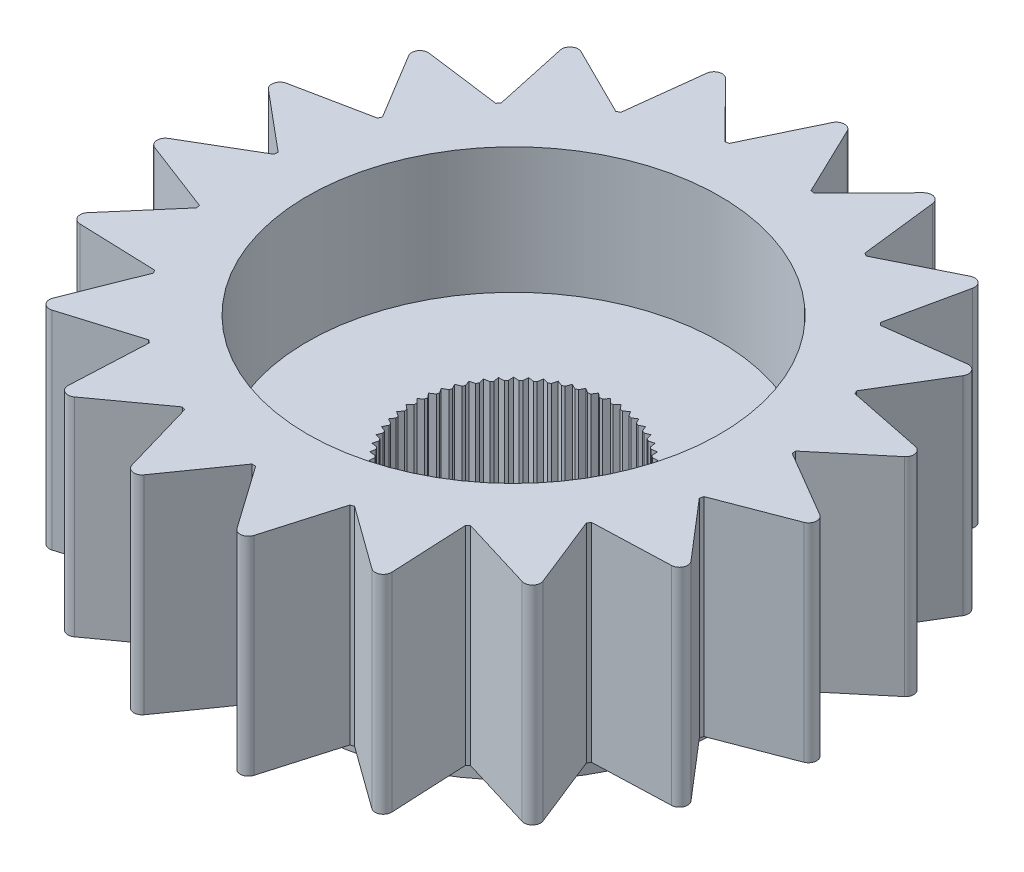
SolidWorks part; units mm, degrees
note: The reader was unsure of these and kept them because the rebuilt part matched: shared geometry of "Sketch1<6>".
ref_plane "Front Plane" through (0, 0, 0) normal (0, 0, 1) x (1, 0, 0)
ref_plane "Top Plane" through (0, 0, 0) normal (0, 1, 0) x (1, 0, 0)
ref_plane "Right Plane" through (0, 0, 0) normal (1, 0, 0) x (0, 0, -1)
sketch "Sketch1" plane through (0, 0, 0) normal (0, 1, 0) x (1, 0, 0)
  line L0 (0.2601, 0.5202) -> (0.2601, 2.8702) construction
  line L1 (0.2601, 2.8702) -> (0.2601, 2.9202) construction
  line L2 (0.1319, 2.9668) -> (0.1293, 3.0168) construction
  line L3 (0.1319, 2.9668) -> (0.2601, 0.5202) construction
  line L5 (0.3883, 2.9668) -> (0.2601, 0.5202) construction
  line L6 (0.3883, 2.9668) -> (0.3909, 3.0168) construction
  line L8 (0.2944, 2.9202) -> (0.2258, 2.9202)
  line L9 (0.3909, 3.0168) -> (0.4769, 2.9106)
  line L10 (0.545, 2.9035) -> (0.4769, 2.9106)
  line L11 (0.6512, 2.9894) -> (0.545, 2.9035)
  line L12 (0.6512, 2.9894) -> (0.7256, 2.8749)
  line L13 (0.7926, 2.8606) -> (0.7256, 2.8749)
  line L14 (0.9071, 2.935) -> (0.7926, 2.8606)
  line L15 (0.9071, 2.935) -> (0.9691, 2.8133)
  line L16 (1.0343, 2.7921) -> (0.9691, 2.8133)
  line L17 (1.156, 2.8541) -> (1.0343, 2.7921)
  line L18 (1.156, 2.8541) -> (1.205, 2.7266)
  line L19 (1.2676, 2.6988) -> (1.205, 2.7266)
  line L20 (1.3951, 2.7477) -> (1.2676, 2.6988)
  line L21 (1.3951, 2.7477) -> (1.4304, 2.6158)
  line L22 (1.4898, 2.5815) -> (1.4304, 2.6158)
  line L23 (1.6217, 2.6169) -> (1.4898, 2.5815)
  line L24 (1.6217, 2.6169) -> (1.6431, 2.482)
  line L25 (1.6985, 2.4417) -> (1.6431, 2.482)
  line L26 (1.8334, 2.463) -> (1.6985, 2.4417)
  line L27 (1.8334, 2.463) -> (1.8405, 2.3267)
  line L28 (1.8915, 2.2808) -> (1.8405, 2.3267)
  line L29 (2.0279, 2.288) -> (1.8915, 2.2808)
  line L30 (2.0279, 2.288) -> (2.0207, 2.1516)
  line L31 (2.0666, 2.1006) -> (2.0207, 2.1516)
  line L32 (2.203, 2.0935) -> (2.0666, 2.1006)
  line L33 (2.203, 2.0935) -> (2.1816, 1.9586)
  line L34 (2.2219, 1.9031) -> (2.1816, 1.9586)
  line L35 (2.3568, 1.8818) -> (2.2219, 1.9031)
  line L36 (2.3568, 1.8818) -> (2.3214, 1.7499)
  line L37 (2.3557, 1.6905) -> (2.3214, 1.7499)
  line L38 (2.4876, 1.6552) -> (2.3557, 1.6905)
  line L39 (2.4876, 1.6552) -> (2.4387, 1.5277)
  line L40 (2.4665, 1.465) -> (2.4387, 1.5277)
  line L41 (2.594, 1.4161) -> (2.4665, 1.465)
  line L42 (2.594, 1.4161) -> (2.532, 1.2944)
  line L43 (2.5532, 1.2292) -> (2.532, 1.2944)
  line L44 (2.6749, 1.1672) -> (2.5532, 1.2292)
  line L45 (2.6749, 1.1672) -> (2.6005, 1.0527)
  line L46 (2.6148, 0.9857) -> (2.6005, 1.0527)
  line L47 (2.7293, 0.9113) -> (2.6148, 0.9857)
  line L48 (2.7293, 0.9113) -> (2.6434, 0.8051)
  line L49 (2.6505, 0.737) -> (2.6434, 0.8051)
  line L50 (2.7567, 0.651) -> (2.6505, 0.737)
  line L51 (2.7567, 0.651) -> (2.6601, 0.5545)
  line L52 (2.6601, 0.4859) -> (2.6601, 0.5545)
  line L53 (2.7567, 0.3893) -> (2.6601, 0.4859)
  line L54 (2.7567, 0.3893) -> (2.6505, 0.3034)
  line L55 (2.6434, 0.2352) -> (2.6505, 0.3034)
  line L56 (2.7293, 0.1291) -> (2.6434, 0.2352)
  line L57 (2.7293, 0.1291) -> (2.6148, 0.0547)
  line L58 (2.6005, -0.0123) -> (2.6148, 0.0547)
  line L59 (2.6749, -0.1269) -> (2.6005, -0.0123)
  line L60 (2.6749, -0.1269) -> (2.5532, -0.1889)
  line L61 (2.532, -0.254) -> (2.5532, -0.1889)
  line L62 (2.594, -0.3757) -> (2.532, -0.254)
  line L63 (2.594, -0.3757) -> (2.4665, -0.4247)
  line L64 (2.4387, -0.4873) -> (2.4665, -0.4247)
  line L65 (2.4876, -0.6148) -> (2.4387, -0.4873)
  line L66 (2.4876, -0.6148) -> (2.3557, -0.6501)
  line L67 (2.3214, -0.7095) -> (2.3557, -0.6501)
  line L68 (2.3568, -0.8414) -> (2.3214, -0.7095)
  line L69 (2.3568, -0.8414) -> (2.2219, -0.8628)
  line L70 (2.1816, -0.9182) -> (2.2219, -0.8628)
  line L71 (2.203, -1.0531) -> (2.1816, -0.9182)
  line L72 (2.203, -1.0531) -> (2.0666, -1.0603)
  line L73 (2.0207, -1.1112) -> (2.0666, -1.0603)
  line L74 (2.0279, -1.2476) -> (2.0207, -1.1112)
  line L75 (2.0279, -1.2476) -> (1.8915, -1.2404)
  line L76 (1.8405, -1.2863) -> (1.8915, -1.2404)
  line L77 (1.8334, -1.4227) -> (1.8405, -1.2863)
  line L78 (1.8334, -1.4227) -> (1.6985, -1.4013)
  line L79 (1.6431, -1.4416) -> (1.6985, -1.4013)
  line L80 (1.6217, -1.5765) -> (1.6431, -1.4416)
  line L81 (1.6217, -1.5765) -> (1.4898, -1.5411)
  line L82 (1.4304, -1.5754) -> (1.4898, -1.5411)
  line L83 (1.3951, -1.7073) -> (1.4304, -1.5754)
  line L84 (1.3951, -1.7073) -> (1.2676, -1.6584)
  line L85 (1.205, -1.6863) -> (1.2676, -1.6584)
  line L86 (1.156, -1.8138) -> (1.205, -1.6863)
  line L87 (1.156, -1.8138) -> (1.0343, -1.7518)
  line L88 (0.9691, -1.7729) -> (1.0343, -1.7518)
  line L89 (0.9071, -1.8946) -> (0.9691, -1.7729)
  line L90 (0.9071, -1.8946) -> (0.7926, -1.8202)
  line L91 (0.7256, -1.8345) -> (0.7926, -1.8202)
  line L92 (0.6512, -1.949) -> (0.7256, -1.8345)
  line L93 (0.6512, -1.949) -> (0.545, -1.8631)
  line L94 (0.4769, -1.8703) -> (0.545, -1.8631)
  line L95 (0.3909, -1.9764) -> (0.4769, -1.8703)
  line L96 (0.3909, -1.9764) -> (0.2944, -1.8798)
  line L97 (0.2258, -1.8798) -> (0.2944, -1.8798)
  line L98 (0.1293, -1.9764) -> (0.2258, -1.8798)
  line L99 (0.1293, -1.9764) -> (0.0433, -1.8703)
  line L100 (-0.0249, -1.8631) -> (0.0433, -1.8703)
  line L101 (-0.131, -1.949) -> (-0.0249, -1.8631)
  line L102 (-0.131, -1.949) -> (-0.2054, -1.8345)
  line L103 (-0.2724, -1.8202) -> (-0.2054, -1.8345)
  line L104 (-0.387, -1.8946) -> (-0.2724, -1.8202)
  line L105 (-0.387, -1.8946) -> (-0.449, -1.7729)
  line L106 (-0.5141, -1.7518) -> (-0.449, -1.7729)
  line L107 (-0.6358, -1.8138) -> (-0.5141, -1.7518)
  line L108 (-0.6358, -1.8138) -> (-0.6848, -1.6863)
  line L109 (-0.7474, -1.6584) -> (-0.6848, -1.6863)
  line L110 (-0.8749, -1.7073) -> (-0.7474, -1.6584)
  line L111 (-0.8749, -1.7073) -> (-0.9102, -1.5754)
  line L112 (-0.9696, -1.5411) -> (-0.9102, -1.5754)
  line L113 (-1.1015, -1.5765) -> (-0.9696, -1.5411)
  line L114 (-1.1015, -1.5765) -> (-1.1229, -1.4416)
  line L115 (-1.1783, -1.4013) -> (-1.1229, -1.4416)
  line L116 (-1.3132, -1.4227) -> (-1.1783, -1.4013)
  line L117 (-1.3132, -1.4227) -> (-1.3204, -1.2863)
  line L118 (-1.3713, -1.2404) -> (-1.3204, -1.2863)
  line L119 (-1.5077, -1.2476) -> (-1.3713, -1.2404)
  line L120 (-1.5077, -1.2476) -> (-1.5005, -1.1112)
  line L121 (-1.5464, -1.0603) -> (-1.5005, -1.1112)
  line L122 (-1.6828, -1.0531) -> (-1.5464, -1.0603)
  line L123 (-1.6828, -1.0531) -> (-1.6614, -0.9182)
  line L124 (-1.7017, -0.8628) -> (-1.6614, -0.9182)
  line L125 (-1.8366, -0.8414) -> (-1.7017, -0.8628)
  line L126 (-1.8366, -0.8414) -> (-1.8012, -0.7095)
  line L127 (-1.8355, -0.6501) -> (-1.8012, -0.7095)
  line L128 (-1.9674, -0.6148) -> (-1.8355, -0.6501)
  line L129 (-1.9674, -0.6148) -> (-1.9185, -0.4873)
  line L130 (-1.9464, -0.4247) -> (-1.9185, -0.4873)
  line L131 (-2.0739, -0.3757) -> (-1.9464, -0.4247)
  line L132 (-2.0739, -0.3757) -> (-2.0119, -0.254)
  line L133 (-2.033, -0.1889) -> (-2.0119, -0.254)
  line L134 (-2.1547, -0.1269) -> (-2.033, -0.1889)
  line L135 (-2.1547, -0.1269) -> (-2.0803, -0.0123)
  line L136 (-2.0946, 0.0547) -> (-2.0803, -0.0123)
  line L137 (-2.2091, 0.1291) -> (-2.0946, 0.0547)
  line L138 (-2.2091, 0.1291) -> (-2.1232, 0.2352)
  line L139 (-2.1303, 0.3034) -> (-2.1232, 0.2352)
  line L140 (-2.2365, 0.3893) -> (-2.1303, 0.3034)
  line L141 (-2.2365, 0.3893) -> (-2.1399, 0.4859)
  line L142 (-2.1399, 0.5545) -> (-2.1399, 0.4859)
  line L143 (-2.2365, 0.651) -> (-2.1399, 0.5545)
  line L144 (-2.2365, 0.651) -> (-2.1303, 0.737)
  line L145 (-2.1232, 0.8051) -> (-2.1303, 0.737)
  line L146 (-2.2091, 0.9113) -> (-2.1232, 0.8051)
  line L147 (-2.2091, 0.9113) -> (-2.0946, 0.9857)
  line L148 (-2.0803, 1.0527) -> (-2.0946, 0.9857)
  line L149 (-2.1547, 1.1672) -> (-2.0803, 1.0527)
  line L150 (-2.1547, 1.1672) -> (-2.033, 1.2292)
  line L151 (-2.0119, 1.2944) -> (-2.033, 1.2292)
  line L152 (-2.0739, 1.4161) -> (-2.0119, 1.2944)
  line L153 (-2.0739, 1.4161) -> (-1.9464, 1.465)
  line L154 (-1.9185, 1.5277) -> (-1.9464, 1.465)
  line L155 (-1.9674, 1.6552) -> (-1.9185, 1.5277)
  line L156 (-1.9674, 1.6552) -> (-1.8355, 1.6905)
  line L157 (-1.8012, 1.7499) -> (-1.8355, 1.6905)
  line L158 (-1.8366, 1.8818) -> (-1.8012, 1.7499)
  line L159 (-1.8366, 1.8818) -> (-1.7017, 1.9031)
  line L160 (-1.6614, 1.9586) -> (-1.7017, 1.9031)
  line L161 (-1.6828, 2.0935) -> (-1.6614, 1.9586)
  line L162 (-1.6828, 2.0935) -> (-1.5464, 2.1006)
  line L163 (-1.5005, 2.1516) -> (-1.5464, 2.1006)
  line L164 (-1.5077, 2.288) -> (-1.5005, 2.1516)
  line L165 (-1.5077, 2.288) -> (-1.3713, 2.2808)
  line L166 (-1.3204, 2.3267) -> (-1.3713, 2.2808)
  line L167 (-1.3132, 2.463) -> (-1.3204, 2.3267)
  line L168 (-1.3132, 2.463) -> (-1.1783, 2.4417)
  line L169 (-1.1229, 2.482) -> (-1.1783, 2.4417)
  line L170 (-1.1015, 2.6169) -> (-1.1229, 2.482)
  line L171 (-1.1015, 2.6169) -> (-0.9696, 2.5815)
  line L172 (-0.9102, 2.6158) -> (-0.9696, 2.5815)
  line L173 (-0.8749, 2.7477) -> (-0.9102, 2.6158)
  line L174 (-0.8749, 2.7477) -> (-0.7474, 2.6988)
  line L175 (-0.6848, 2.7266) -> (-0.7474, 2.6988)
  line L176 (-0.6358, 2.8541) -> (-0.6848, 2.7266)
  line L177 (-0.6358, 2.8541) -> (-0.5141, 2.7921)
  line L178 (-0.449, 2.8133) -> (-0.5141, 2.7921)
  line L179 (-0.387, 2.935) -> (-0.449, 2.8133)
  line L180 (-0.387, 2.935) -> (-0.2724, 2.8606)
  line L181 (-0.2054, 2.8749) -> (-0.2724, 2.8606)
  line L182 (-0.131, 2.9894) -> (-0.2054, 2.8749)
  line L183 (-0.131, 2.9894) -> (-0.0249, 2.9035)
  line L184 (0.0433, 2.9106) -> (-0.0249, 2.9035)
  line L185 (0.1293, 3.0168) -> (0.0433, 2.9106)
  line L186 (0.1293, 3.0168) -> (0.2258, 2.9202)
  line L187 (0.2944, 2.9202) -> (0.3909, 3.0168)
  line L188 (0.1293, 3.0168) -> (-0.0037, 5.5533) construction
  circle A0 centre (0.2601, 0.5202) radius 2.5
  circle A1 centre (0.2601, 0.5202) radius 2.35 construction
  arc A2 (0.1293, 3.0168) -> (0.3909, 3.0168) centre (0.2601, 0.5202) cw
  arc A3 (0.3909, 3.0168) -> (0.6512, 2.9894) centre (0.2601, 0.5202) cw
  arc A4 (0.6512, 2.9894) -> (0.9071, 2.935) centre (0.2601, 0.5202) cw
  arc A5 (0.9071, 2.935) -> (1.156, 2.8541) centre (0.2601, 0.5202) cw
  arc A6 (1.156, 2.8541) -> (1.3951, 2.7477) centre (0.2601, 0.5202) cw
  arc A7 (1.3951, 2.7477) -> (1.6217, 2.6169) centre (0.2601, 0.5202) cw
  arc A8 (1.6217, 2.6169) -> (1.8334, 2.463) centre (0.2601, 0.5202) cw
  arc A9 (1.8334, 2.463) -> (2.0279, 2.288) centre (0.2601, 0.5202) cw
  arc A10 (2.0279, 2.288) -> (2.203, 2.0935) centre (0.2601, 0.5202) cw
  arc A11 (2.203, 2.0935) -> (2.3568, 1.8818) centre (0.2601, 0.5202) cw
  arc A12 (2.3568, 1.8818) -> (2.4876, 1.6552) centre (0.2601, 0.5202) cw
  arc A13 (2.4876, 1.6552) -> (2.594, 1.4161) centre (0.2601, 0.5202) cw
  arc A14 (2.594, 1.4161) -> (2.6749, 1.1672) centre (0.2601, 0.5202) cw
  arc A15 (2.6749, 1.1672) -> (2.7293, 0.9113) centre (0.2601, 0.5202) cw
  arc A16 (2.7293, 0.9113) -> (2.7567, 0.651) centre (0.2601, 0.5202) cw
  arc A17 (2.7567, 0.651) -> (2.7567, 0.3893) centre (0.2601, 0.5202) cw
  arc A18 (2.7567, 0.3893) -> (2.7293, 0.1291) centre (0.2601, 0.5202) cw
  arc A19 (2.7293, 0.1291) -> (2.6749, -0.1269) centre (0.2601, 0.5202) cw
  arc A20 (2.6749, -0.1269) -> (2.594, -0.3757) centre (0.2601, 0.5202) cw
  arc A21 (2.594, -0.3757) -> (2.4876, -0.6148) centre (0.2601, 0.5202) cw
  arc A22 (2.4876, -0.6148) -> (2.3568, -0.8414) centre (0.2601, 0.5202) cw
  arc A23 (2.3568, -0.8414) -> (2.203, -1.0531) centre (0.2601, 0.5202) cw
  arc A24 (2.203, -1.0531) -> (2.0279, -1.2476) centre (0.2601, 0.5202) cw
  arc A25 (2.0279, -1.2476) -> (1.8334, -1.4227) centre (0.2601, 0.5202) cw
  arc A26 (1.8334, -1.4227) -> (1.6217, -1.5765) centre (0.2601, 0.5202) cw
  arc A27 (1.6217, -1.5765) -> (1.3951, -1.7073) centre (0.2601, 0.5202) cw
  arc A28 (1.3951, -1.7073) -> (1.156, -1.8138) centre (0.2601, 0.5202) cw
  arc A29 (1.156, -1.8138) -> (0.9071, -1.8946) centre (0.2601, 0.5202) cw
  arc A30 (0.9071, -1.8946) -> (0.6512, -1.949) centre (0.2601, 0.5202) cw
  arc A31 (0.6512, -1.949) -> (0.3909, -1.9764) centre (0.2601, 0.5202) cw
  arc A32 (0.3909, -1.9764) -> (0.1293, -1.9764) centre (0.2601, 0.5202) cw
  arc A33 (0.1293, -1.9764) -> (-0.131, -1.949) centre (0.2601, 0.5202) cw
  arc A34 (-0.131, -1.949) -> (-0.387, -1.8946) centre (0.2601, 0.5202) cw
  arc A35 (-0.387, -1.8946) -> (-0.6358, -1.8138) centre (0.2601, 0.5202) cw
  arc A36 (-0.6358, -1.8138) -> (-0.8749, -1.7073) centre (0.2601, 0.5202) cw
  arc A37 (-0.8749, -1.7073) -> (-1.1015, -1.5765) centre (0.2601, 0.5202) cw
  arc A38 (-1.1015, -1.5765) -> (-1.3132, -1.4227) centre (0.2601, 0.5202) cw
  arc A39 (-1.3132, -1.4227) -> (-1.5077, -1.2476) centre (0.2601, 0.5202) cw
  arc A40 (-1.5077, -1.2476) -> (-1.6828, -1.0531) centre (0.2601, 0.5202) cw
  arc A41 (-1.6828, -1.0531) -> (-1.8366, -0.8414) centre (0.2601, 0.5202) cw
  arc A42 (-1.8366, -0.8414) -> (-1.9674, -0.6148) centre (0.2601, 0.5202) cw
  arc A43 (-1.9674, -0.6148) -> (-2.0739, -0.3757) centre (0.2601, 0.5202) cw
  arc A44 (-2.0739, -0.3757) -> (-2.1547, -0.1269) centre (0.2601, 0.5202) cw
  arc A45 (-2.1547, -0.1269) -> (-2.2091, 0.1291) centre (0.2601, 0.5202) cw
  arc A46 (-2.2091, 0.1291) -> (-2.2365, 0.3893) centre (0.2601, 0.5202) cw
  arc A47 (-2.2365, 0.3893) -> (-2.2365, 0.651) centre (0.2601, 0.5202) cw
  arc A48 (-2.2365, 0.651) -> (-2.2091, 0.9113) centre (0.2601, 0.5202) cw
  arc A49 (-2.2091, 0.9113) -> (-2.1547, 1.1672) centre (0.2601, 0.5202) cw
  arc A50 (-2.1547, 1.1672) -> (-2.0739, 1.4161) centre (0.2601, 0.5202) cw
  arc A51 (-2.0739, 1.4161) -> (-1.9674, 1.6552) centre (0.2601, 0.5202) cw
  arc A52 (-1.9674, 1.6552) -> (-1.8366, 1.8818) centre (0.2601, 0.5202) cw
  arc A53 (-1.8366, 1.8818) -> (-1.6828, 2.0935) centre (0.2601, 0.5202) cw
  arc A54 (-1.6828, 2.0935) -> (-1.5077, 2.288) centre (0.2601, 0.5202) cw
  arc A55 (-1.5077, 2.288) -> (-1.3132, 2.463) centre (0.2601, 0.5202) cw
  arc A56 (-1.3132, 2.463) -> (-1.1015, 2.6169) centre (0.2601, 0.5202) cw
  arc A57 (-1.1015, 2.6169) -> (-0.8749, 2.7477) centre (0.2601, 0.5202) cw
  arc A58 (-0.8749, 2.7477) -> (-0.6358, 2.8541) centre (0.2601, 0.5202) cw
  arc A59 (-0.6358, 2.8541) -> (-0.387, 2.935) centre (0.2601, 0.5202) cw
  arc A60 (-0.387, 2.935) -> (-0.131, 2.9894) centre (0.2601, 0.5202) cw
  arc A61 (-0.131, 2.9894) -> (0.1293, 3.0168) centre (0.2601, 0.5202) cw
  circle A63 centre (0.2601, 0.5202) radius 5.04
  point P251 (0.2601, 0.5202)
  dimension "D1" = 5
  dimension "D3" = 2.54
  dimension "D2" = 60
extrude "Boss-Extrude3" add sketch "Sketch1" along normal blind 3.2 contours A63
sketch "Sketch7" plane through (0, 3.2, 0) normal (0, 1, 0) x (1, 0, 0)
  line L0 (0.2601, 0.5202) -> (0.2601, 6.8702) construction
  line L1 (0.2601, 6.8702) -> (0.2601, 8.8702) construction
  line L2 (0.2601, 8.8702) -> (-0.7399, 6.7909)
  line L3 (0.2601, 8.8702) -> (1.2601, 6.7909)
  line L4 (2.9713, 8.4178) -> (1.3504, 6.7759)
  line L5 (2.9713, 8.4178) -> (3.242, 6.1265)
  line L6 (5.3888, 7.1095) -> (3.3225, 6.0829)
  line L7 (5.3888, 7.1095) -> (4.9008, 4.8545)
  line L8 (7.2504, 5.0872) -> (4.9628, 4.7871)
  line L9 (7.2504, 5.0872) -> (6.0567, 3.1128)
  line L10 (8.3546, 2.57) -> (6.0935, 3.029)
  line L11 (8.3546, 2.57) -> (6.5845, 1.0902)
  line L12 (8.5816, -0.1694) -> (6.592, 0.9989)
  line L13 (8.5816, -0.1694) -> (6.4269, -0.9942)
  line L14 (7.9068, -2.834) -> (6.4044, -1.083)
  line L15 (7.9068, -2.834) -> (5.601, -2.9145)
  line L16 (6.4034, -5.1351) -> (5.5509, -2.9912)
  line L17 (6.4034, -5.1351) -> (4.1964, -4.4626)
  line L18 (4.2343, -6.8234) -> (4.1241, -4.5188)
  line L19 (4.2343, -6.8234) -> (2.3652, -5.4707)
  line L20 (1.6345, -7.7159) -> (2.2786, -5.5005)
  line L21 (1.6345, -7.7159) -> (0.3059, -5.8297)
  line L22 (-1.1143, -7.7159) -> (0.2143, -5.8297)
  line L23 (-1.1143, -7.7159) -> (-1.7584, -5.5005)
  line L24 (-3.7141, -6.8234) -> (-1.845, -5.4707)
  line L25 (-3.7141, -6.8234) -> (-3.6039, -4.5188)
  line L26 (-5.8832, -5.1351) -> (-3.6762, -4.4626)
  line L27 (-5.8832, -5.1351) -> (-5.0307, -2.9912)
  line L28 (-7.3866, -2.834) -> (-5.0808, -2.9145)
  line L29 (-7.3866, -2.834) -> (-5.8842, -1.083)
  line L30 (-8.0614, -0.1694) -> (-5.9067, -0.9942)
  line L31 (-8.0614, -0.1694) -> (-6.0718, 0.9989)
  line L32 (-7.8344, 2.57) -> (-6.0643, 1.0902)
  line L33 (-7.8344, 2.57) -> (-5.5733, 3.029)
  line L34 (-6.7302, 5.0872) -> (-5.5365, 3.1128)
  line L35 (-6.7302, 5.0872) -> (-4.4426, 4.7871)
  line L36 (-4.8686, 7.1095) -> (-4.3806, 4.8545)
  line L37 (-4.8686, 7.1095) -> (-2.8024, 6.0829)
  line L38 (-2.4511, 8.4178) -> (-2.7218, 6.1265)
  line L39 (-2.4511, 8.4178) -> (-0.8302, 6.7759)
  circle A0 centre (0.2601, 0.5202) radius 6.35
  circle A1 centre (0.2601, 0.5202) radius 6.35
  circle A2 centre (0.2601, 0.5202) radius 6.35
  circle A3 centre (0.2601, 0.5202) radius 6.35
  circle A4 centre (0.2601, 0.5202) radius 6.35
  circle A5 centre (0.2601, 0.5202) radius 6.35
  circle A6 centre (0.2601, 0.5202) radius 6.35
  circle A7 centre (0.2601, 0.5202) radius 6.35
  circle A8 centre (0.2601, 0.5202) radius 6.35
  circle A9 centre (0.2601, 0.5202) radius 6.35
  circle A10 centre (0.2601, 0.5202) radius 6.35
  circle A11 centre (0.2601, 0.5202) radius 6.35
  circle A12 centre (0.2601, 0.5202) radius 6.35
  circle A13 centre (0.2601, 0.5202) radius 6.35
  circle A14 centre (0.2601, 0.5202) radius 6.35
  point P66 (0.2601, 0.5202)
  point P79 (0.2601, 0.5202)
  point P227 (0.2601, 0.5202)
  dimension "D1" = 12.7
  dimension "D2" = 2
  dimension "D3" = 2
extrude "Boss-Extrude4" add sketch "Sketch7" along normal blind 3.08 and the other way blind 2
extrude "Cut-Extrude2" cut sketch "Sketch1<6>" along normal through all contours L187 L8 L186 L185 L184 L183 L182 L181 L180 L179 L178 L177 L176 L175 L174 L173 L172 L171 L170 L169 L168 L167 L166 L165 L164 L163 L162 L161 L160 L159 L158 L157 L156 L155 L154 L153 L152 L151 L150 L149 L148 L147 L146 L145 L144 L143 L142 L141 L140 L139 L138
sketch "Sketch1<6>" plane through (0, 0, 0) normal (0, 1, 0) x (1, 0, 0) same geometry as "Sketch1"
fillet "Fillet1" radius 0.2 19 edges at (0.2601, 3.74, -8.8702) (-3.7141, 3.74, 6.8234) (5.3888, 3.74, -7.1095) (2.9713, 3.74, -8.4178) (7.2504, 3.74, -5.0872) (8.3546, 3.74, -2.57) (8.5816, 3.74, 0.1694) (7.9068, 3.74, 2.834) (6.4034, 3.74, 5.1351) (4.2343, 3.74, 6.8234) (1.6345, 3.74, 7.7159) (-1.1143, 3.74, 7.7159) (-5.8832, 3.74, 5.1351) (-7.3866, 3.74, 2.834) (-8.0614, 3.74, 0.1694) (-7.8344, 3.74, -2.57) (-6.7302, 3.74, -5.0872) (-2.4511, 3.74, -8.4178) (-4.8686, 3.74, -7.1095)
sketch "Sketch8" plane through (0, 6.28, 0) normal (0, 1, 0) x (1, 0, 0)
  circle A0 centre (0.2601, 0.5202) radius 8.0886 construction
  circle A1 centre (0.2601, 0.5202) radius 5.04 construction
  arc A3 (0.4403, 8.4954) -> (0.0799, 8.4954) centre (0.2601, 8.4087) ccw construction
